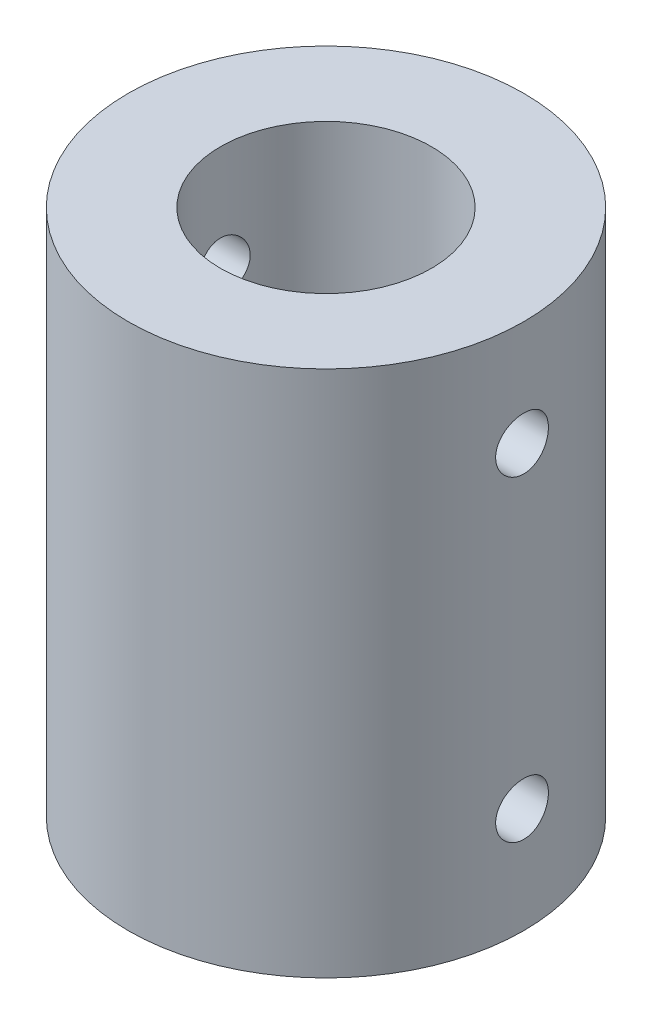
SolidWorks part; units mm, degrees
ref_plane "Front Plane" through (0, 0, 0) normal (0, 0, 1) x (1, 0, 0)
ref_plane "Top Plane" through (0, 0, 0) normal (0, 1, 0) x (1, 0, 0)
ref_plane "Right Plane" through (0, 0, 0) normal (1, 0, 0) x (0, 0, -1)
sketch "Sketch1" plane through (0, 0, 0) normal (0, 1, 0) x (1, 0, 0)
  circle A0 centre (0, 0) radius 7.5
  circle A1 centre (0, 0) radius 4
  circle A2 centre (0, 0) radius 2.5
  dimension "D1" = 15
  dimension "D2" = 8
  dimension "D3" = 5
extrude "Boss-Extrude2" add sketch "Sketch1" along normal blind 10 contours A0 A1 region at (-7.2879, 0, 0)
extrude "Boss-Extrude3" add sketch "Sketch1<3>" against normal blind 10 contours A0 A1 | A1 A2 region at (-7.2879, 0, 0) region at (-3.8869, 0, 0)
sketch "Sketch1<3>" plane through (0, 0, 0) normal (0, 1, 0) x (1, 0, 0) same geometry as "Sketch1"
sketch "Sketch2" plane through (0, 0, 0) normal (1, 0, 0) x (0, 0, -1)
  line L0 (0, 6) -> (0, -6) construction
  circle A0 centre (0, 6) radius 1
  circle A1 centre (0, -6) radius 1
  point P4 (0, 0)
  dimension "D1" = 2
  dimension "D2" = 12
extrude "Cut-Extrude1" cut sketch "Sketch2" against normal through all both and the other way through all
